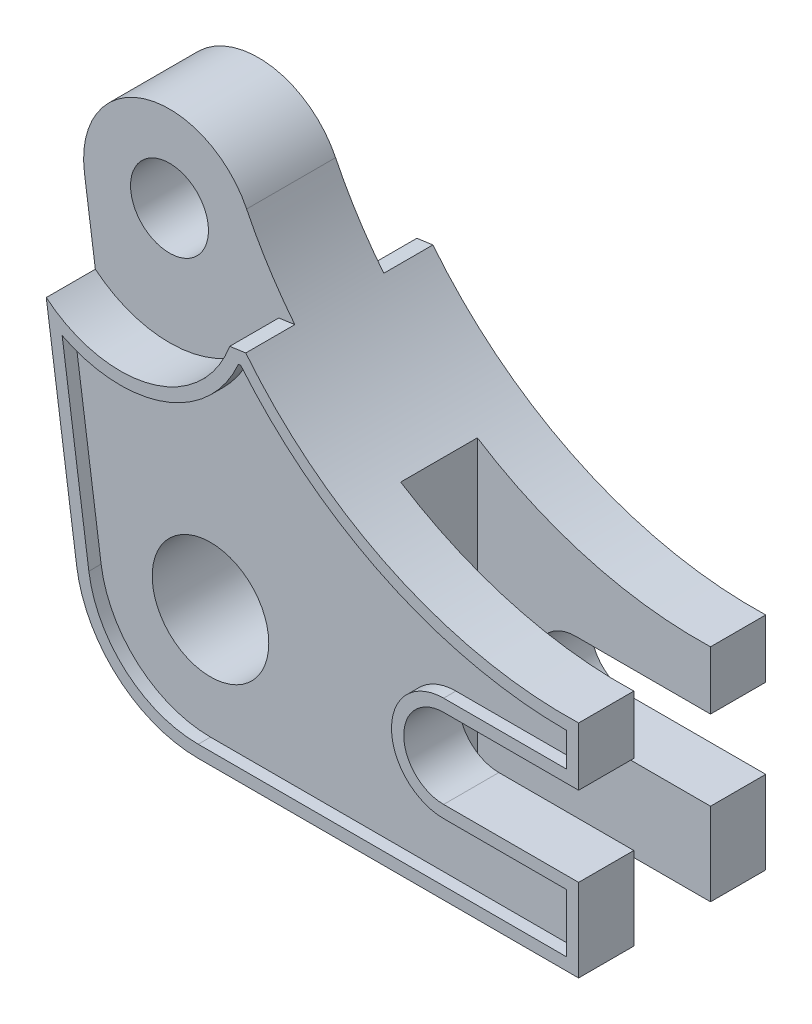
SolidWorks part; units mm, degrees
ref_plane "Front Plane" through (0, 0, 0) normal (0, 0, 1) x (1, 0, 0)
ref_plane "Top Plane" through (0, 0, 0) normal (0, 1, 0) x (1, 0, 0)
ref_plane "Right Plane" through (0, 0, 0) normal (1, 0, 0) x (0, 0, -1)
sketch "Sketch1" plane through (0, 0, 0) normal (0, 0, 1) x (1, 0, 0)
  line L0 (62, -20) -> (62, -6.5)
  line L1 (-19.807, -2.7719) -> (-26.547, 45.39)
  line L2 (62, -6.5) -> (40, -6.5)
  line L3 (40, 6.5) -> (62, 6.5)
  line L4 (-12.6821, 47.3304) -> (0, 0) construction
  line L5 (0, -20) -> (62, -20)
  line L6 (62, 6.5) -> (62, 16)
  line L7 (5.1369, 40.7364) -> (7.749, 41.1019)
  arc A0 (40, -6.5) -> (40, 6.5) centre (40, 0) cw
  circle A1 centre (-12.6821, 47.3304) radius 6.35
  circle A2 centre (0, 0) radius 9.5
  arc A3 (-0.1103, 53.4906) -> (-26.547, 45.39) centre (-12.6821, 47.3304) ccw
  arc A4 (-19.807, -2.7719) -> (0, -20) centre (0, 0) ccw
  arc A5 (62, 16) -> (-0.1103, 53.4906) centre (60.055, 82.9718) cw
  arc A6 (5.1369, 40.7364) -> (-24.7667, 32.6688) centre (-12.6821, 47.3304) cw
  point P20 (-20, 0)
  point P21 (0, 0)
  point P22 (0, 0)
  dimension "D2" = 6.5
  dimension "D3" = 12.7
  dimension "D4" = 19
  dimension "D6" = 40
  dimension "D7" = 28
  dimension "D10" = 67
  dimension "D14" = 19
  dimension "D1" = 22
  dimension "D5" = 49
  dimension "D8" = 15
  dimension "D9" = 62
  dimension "D11" = 20
  dimension "D12" = 36
  dimension "D13" = 9
extrude "Boss-Extrude1" add sketch "Sketch1" along normal mid plane 26.5 contours L7 A6 A2 L1 A4 L5 L0 L2 A0 L3 L6 A5 region at (16.1882, 5.3747, 0)
extrude "Boss-Extrude2" add sketch "Sketch1<3>" along normal mid plane 14.5 contours A1 A6 L7 A5 A3 L1 region at (-25.1846, 39.0955, 0)
sketch "Sketch1<3>" plane through (0, 0, 0) normal (0, 0, 1) x (1, 0, 0) same geometry as "Sketch1"
ref_plane "Plane1" through (0, 0, 0) normal (0, 0, 1) x (1, 0, 0)
sketch "Sketch2" plane through (0, 0, 0) normal (0, 0, 1) x (1, 0, 0)
  line L0 (24, -20) -> (24, 26.5002)
  line L1 (0, -20) -> (62, -20) construction
  line L2 (62, -20) -> (62, -6.5) construction
  line L10 (7.749, 41.1019) -> (5.1369, 40.7364)
  line L11 (-24.7667, 32.6688) -> (-19.807, -2.7719)
  line L12 (0, -20) -> (62, -20)
  line L13 (62, -20) -> (62, -6.5)
  line L14 (62, -6.5) -> (40, -6.5)
  line L15 (40, 6.5) -> (62, 6.5)
  line L16 (62, 6.5) -> (62, 16)
  line L19 (24, -20) -> (62, -20)
  line L20 (62, -20) -> (62, -6.5)
  line L21 (62, -6.5) -> (40, -6.5)
  line L22 (40, 6.5) -> (62, 6.5)
  line L23 (62, 6.5) -> (62, 16)
  arc A0 (7.749, 41.1019) -> (62, 16) centre (60.055, 82.9718) ccw construction
  arc A5 (-24.7667, 32.6688) -> (5.1369, 40.7364) centre (-12.6821, 47.3304) ccw
  arc A6 (-19.807, -2.7719) -> (0, -20) centre (0, 0) ccw
  arc A7 (40, 6.5) -> (40, -6.5) centre (40, 0) ccw
  arc A8 (7.749, 41.1019) -> (62, 16) centre (60.055, 82.9718) ccw
  arc A11 (40, 6.5) -> (40, -6.5) centre (40, 0) ccw
  arc A12 (24, 26.5002) -> (62, 16) centre (60.055, 82.9718) ccw
  dimension "D1" = 38
  dimension "D2" = 0
extrude "Cut-Extrude1" cut sketch "Sketch2" against normal blind 6.25 and the other way blind 6.25 contours A12 L0 L19 L20 L21 A11 L22 L23 region at (24.6005, 3.2501, 0)
sketch "Sketch3" plane through (0, 0, 13.25) normal (0, 0, 1) x (1, 0, 0)
  line L14 (6.9099, 38.965) -> (6.5583, 38.9158)
  line L15 (-22.1778, 28.5999) -> (-17.8263, -2.4947)
  line L16 (0, -18) -> (60, -18)
  line L17 (60, -18) -> (60, -8.5)
  line L18 (60, -8.5) -> (40, -8.5)
  line L19 (40, 8.5) -> (60, 8.5)
  line L20 (60, 8.5) -> (60, 13.9718)
  line L22 (-22.1778, 28.5999) -> (-17.8263, -2.4947)
  line L23 (0, -18) -> (60, -18)
  line L24 (60, -18) -> (60, -8.5)
  line L25 (60, -8.5) -> (40, -8.5)
  line L26 (40, 8.5) -> (60, 8.5)
  line L27 (60, 8.5) -> (60, 13.9718)
  line L29 (6.9099, 38.965) -> (6.5583, 38.9158)
  arc A8 (-22.1778, 28.5999) -> (6.5583, 38.9158) centre (-12.6821, 47.3304) ccw
  arc A9 (-17.8263, -2.4947) -> (0, -18) centre (0, 0) ccw
  arc A10 (40, 8.5) -> (40, -8.5) centre (40, 0) ccw
  arc A11 (6.9099, 38.965) -> (60, 13.9718) centre (60.055, 82.9718) ccw
  arc A13 (-17.8263, -2.4947) -> (0, -18) centre (0, 0) ccw
  arc A14 (40, 8.5) -> (40, -8.5) centre (40, 0) ccw
  arc A15 (6.9099, 38.965) -> (60, 13.9718) centre (60.055, 82.9718) ccw
  arc A19 (-22.1778, 28.5999) -> (6.5583, 38.9158) centre (-12.6821, 47.3304) ccw
  line M13 (7.749, 41.1019) -> (5.1369, 40.7364)
  arc M14 (5.1369, 40.7364) -> (-24.7667, 32.6688) centre (-12.6821, 47.3304) cw
  line M15 (-24.7667, 32.6688) -> (-19.807, -2.7719)
  arc M16 (-19.807, -2.7719) -> (0, -20) centre (0, 0) ccw
  line M17 (0, -20) -> (62, -20)
  line M18 (62, -20) -> (62, -6.5)
  line M19 (62, -6.5) -> (40, -6.5)
  arc M20 (40, -6.5) -> (40, 6.5) centre (40, 0) cw
  line M21 (40, 6.5) -> (62, 6.5)
  line M22 (62, 6.5) -> (62, 16)
  arc M23 (62, 16) -> (7.749, 41.1019) centre (60.055, 82.9718) cw
  dimension "D1" = 2
extrude "Boss-Extrude3" add sketch "Sketch3" along normal blind 2 contours L22 A19 L29 A15 L27 L26 A14 L25 L24 L23 A13 M23 M13 M14 M15 M16 M17 M18 M19 M20 M21 M22 region at (31.4743, 21.2023, 13.25)
mirror "Mirror1" about plane through (0, 0, 0) normal (0, 0, 1) of bodies 104
